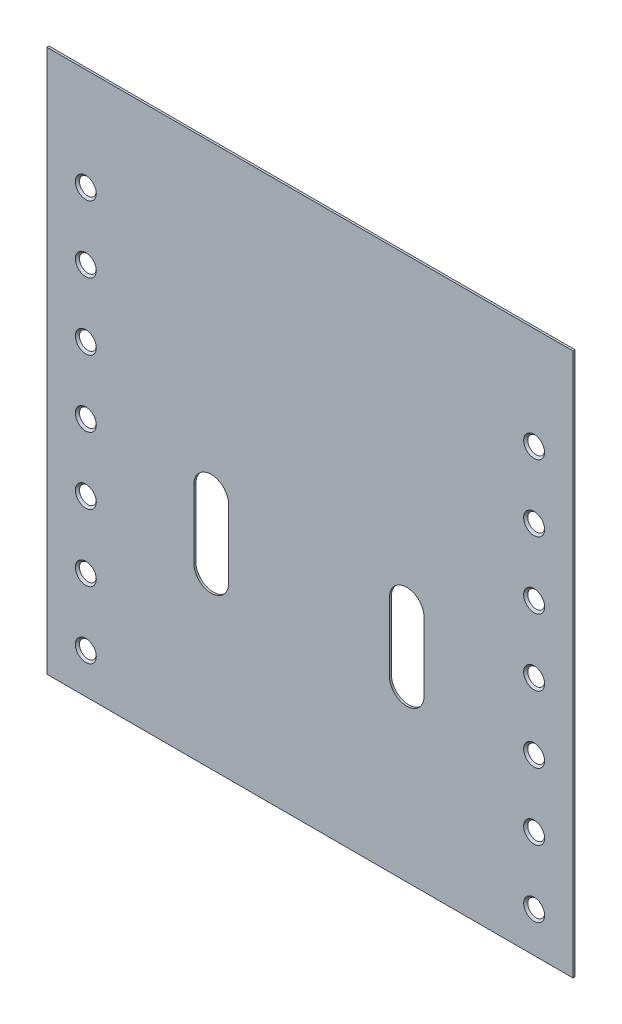
SolidWorks part; units mm, degrees
ref_plane "Front Plane" through (0, 0, 0) normal (0, 0, 1) x (1, 0, 0)
ref_plane "Top Plane" through (0, 0, 0) normal (0, 1, 0) x (1, 0, 0)
ref_plane "Right Plane" through (0, 0, 0) normal (1, 0, 0) x (0, 0, -1)
sketch "Sketch1" plane through (0, 0, 0) normal (0, 0, -1) x (1, 0, 0)
  line L1 (-203.2, 237) -> (-6.35, 237)
  line L2 (-203.2, 237) -> (-203.2, 33.8)
  line L3 (-203.2, 33.8) -> (-6.35, 33.8)
  line L4 (-6.35, 237) -> (-6.35, 33.8)
  dimension "D2" = 196.85
  dimension "D3" = 203.2
extrude "Boss-Extrude1" add sketch "Sketch1" along normal blind 0.7747
sketch "Sketch2" plane through (0, 0, -0.7747) normal (0, 0, -1) x (1, 0, 0)
  line L0 (-141.7213, 180) -> (-141.7213, 141.5) construction
  line L1 (-6.35, 237) -> (-203.2, 237) construction
  line L2 (-141.7213, 180) -> (-141.7213, 237) construction
  line L3 (-141.7213, 173.5) -> (-141.7213, 148) construction
  line L6 (-135.2213, 173.5) -> (-135.2213, 148)
  line L7 (-148.2213, 173.5) -> (-148.2213, 148)
  line L8 (-141.7213, 160.75) -> (-203.2, 160.75) construction
  line L9 (-203.2, 237) -> (-203.2, 33.8) construction
  line L10 (-68.5693, 180) -> (-68.5693, 141.5) construction
  line L11 (-68.5693, 180) -> (-68.5693, 237) construction
  line L12 (-68.5693, 173.5) -> (-68.5693, 148) construction
  line L15 (-141.7213, 160.75) -> (-68.5693, 160.75) construction
  line L16 (-62.0693, 173.5) -> (-62.0693, 148)
  line L17 (-75.0693, 173.5) -> (-75.0693, 148)
  arc A2 (-135.2213, 173.5) -> (-148.2213, 173.5) centre (-141.7213, 173.5) ccw
  arc A3 (-148.2213, 148) -> (-135.2213, 148) centre (-141.7213, 148) ccw
  arc A6 (-62.0693, 173.5) -> (-75.0693, 173.5) centre (-68.5693, 173.5) ccw
  arc A7 (-75.0693, 148) -> (-62.0693, 148) centre (-68.5693, 148) ccw
  point P5 (-141.7213, 160.75)
  point P18 (-68.5693, 160.75)
  dimension "D4" = 6.5
  dimension "D6" = 57
  dimension "D5" = 6.5
  dimension "D1" = 73.152
  dimension "D2" = 57
  dimension "D3" = 38.5
  dimension "D8" = 38.5
extrude "Cut-Extrude7" cut sketch "Sketch2" against normal through all
ref_plane "Plane1" through (-104.775, 0, 0) normal (1, 0, 0) x (0, 0, -1)
sketch "Sketch4" plane through (0, 0, 0) normal (0, 0, 1) x (1, 0, 0)
  line L0 (-203.2, -33.8) -> (-6.35, -33.8) construction
  line L1 (-6.35, -33.8) -> (-203.2, -33.8)
  line L2 (-6.35, -33.8) -> (-6.35, -34.4096)
  line L3 (-6.35, -34.4096) -> (-203.2, -34.4096)
  line L4 (-203.2, -33.8) -> (-203.2, -34.4096)
  line L5 (-6.35, -237) -> (-6.35, 2) construction
  line L6 (-203.2, 2) -> (-203.2, -237) construction
  dimension "D1" = 0.6096
extrude "Boss-Extrude2" add sketch "Sketch4" along normal blind 12
sketch "Sketch8" plane through (0, 0, -0.7747) normal (0, 0, -1) x (-1, 0, 0)
  circle A0 centre (185.47, -222) radius 3.75
  circle A1 centre (185.47, -197) radius 3.75
  circle A2 centre (185.47, -172) radius 3.75
  circle A3 centre (185.47, -147) radius 3.75
  circle A4 centre (185.47, -122) radius 3.75
  circle A5 centre (185.47, -97) radius 3.75
  dimension "D1" = 7.5
sketch "Sketch13" plane through (0, 0, 12) normal (0, 0, 1) x (1, 0, 0)
  line L1 (-6.35, -34.4096) -> (-203.2, -34.4096)
  line L2 (-6.35, -34.4096) -> (-6.35, -33.8)
  line L3 (-6.35, -33.8) -> (-203.2, -33.8)
  line L4 (-203.2, -34.4096) -> (-203.2, -33.8)
sketch "Sketch14" plane through (0, 0, 0) normal (0, 0, 1) x (1, 0, 0)
  line L0 (-6.35, -34.4096) -> (-6.35, -237) construction
  line L1 (-6.35, -59.904) -> (-203.2, -59.904)
  line L2 (-6.35, -59.904) -> (-6.35, -47.966)
  line L3 (-6.35, -47.966) -> (-203.2, -47.966)
  line L4 (-203.2, -59.904) -> (-203.2, -47.966)
  line L5 (-203.2, -237) -> (-203.2, -34.4096) construction
  dimension "D1" = 11.938
extrude "Boss-Extrude3" add sketch "Sketch14" against normal up to surface (0.7747 mm away) up to face at (-141.7213, -160.75, -0.7747)
extrude "Cut-Extrude9" cut sketch "Sketch13" against normal up to surface (12 mm away) up to face at (-68.5693, -160.75, 0)
hole_wizard "CSK for M3 Flat Head Machine Screw3" positions "Sketch15" profile "Sketch16" countersink size "M3" standard "ANSI Metric" end condition through all
sketch "Sketch15" plane through (0, 0, 0) normal (0, 0, 1) x (1, 0, 0)
  point P18 (-188.645, -72)
  point P21 (-188.645, -222)
  point P24 (-188.645, -197)
  point P27 (-188.645, -172)
  point P30 (-188.645, -147)
  point P33 (-188.645, -122)
  point P36 (-188.645, -97)
  point P39 (-188.645, -72)
sketch "Sketch16" plane through (-188.645, -72, 0) normal (1, 0, 0) x (0, -1, 0)
  line L0 (0, 0) -> (0, 0.7747)
  line L1 (0, 0.7747) -> (1.7, 0.7747)
  line L2 (1.7, 0.7747) -> (1.7, 2.212)
  line L3 (1.7, 2.212) -> (3.912, 0)
  line L5 (3.912, 0) -> (0, 0)
  line L6 (-1.7, 2.212) -> (-3.912, 0) construction
  line L11 (0, -6.35) -> (0, 107.95) construction
  dimension "Thru Hole Dia." = 3.4
  dimension "Thru Hole Depth" = 0.7747
  dimension "Near C'Sink Dia." = 7.824
  dimension "Near C'Sink Angle" = 90
ref_plane "Plane2" through (-104.775, 0, 0) normal (1, 0, 0) x (0, 0, -1)
mirror "Mirror1" about plane through (-104.775, 0, 0) normal (1, 0, 0) of "CSK for M3 Flat Head Machine Screw3"
